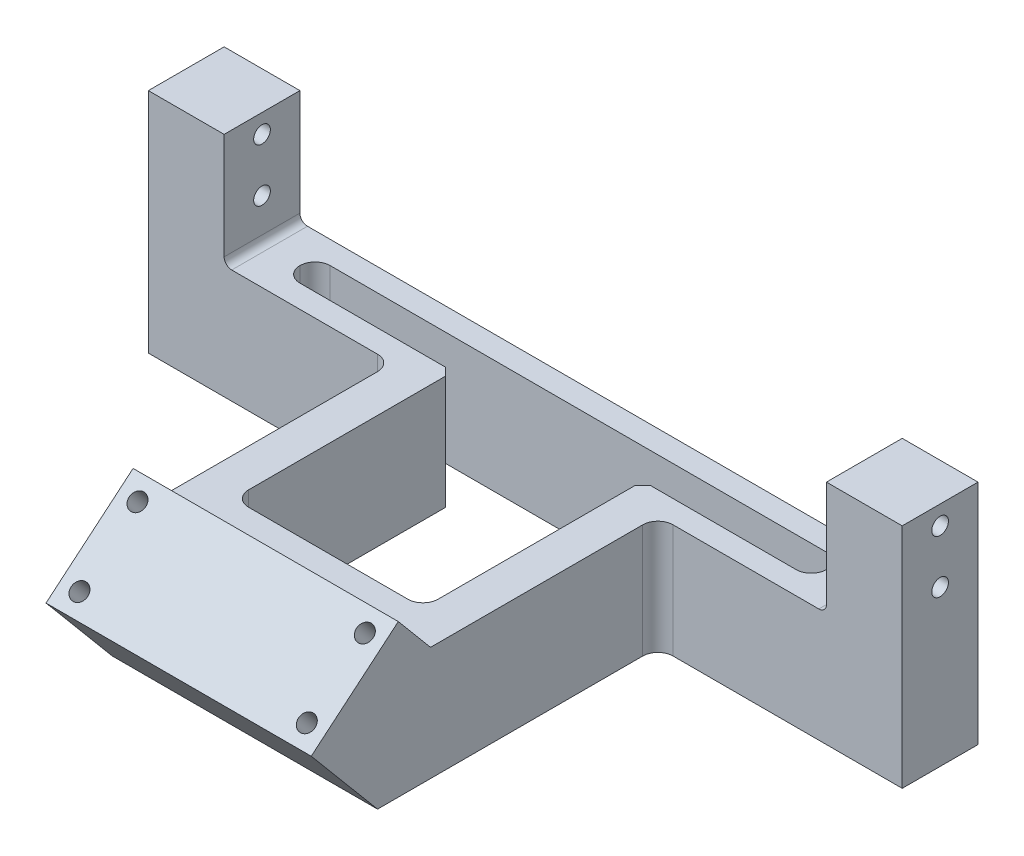
SolidWorks part; units mm, degrees
material "PLA"
ref_plane "Front Plane" through (0, 0, 0) normal (0, 0, 1) x (1, 0, 0)
ref_plane "Top Plane" through (0, 0, 0) normal (0, 1, 0) x (1, 0, 0)
ref_plane "Right Plane" through (0, 0, 0) normal (1, 0, 0) x (0, 0, -1)
sketch "Sketch1" plane through (0, 0, 0) normal (0, 0, 1) x (1, 0, 0)
  line L0 (63.1698, 0) -> (-63.1698, 0)
  line L1 (-63.1698, 0) -> (-63.1698, 38.1)
  line L2 (-63.1698, 38.1) -> (-50.4698, 38.1)
  line L3 (-50.4698, 38.1) -> (-50.4698, 19.05)
  line L4 (-50.4698, 19.05) -> (50.4698, 19.05)
  line L5 (0, 19.05) -> (0, 0) construction
  line L6 (50.4698, 38.1) -> (50.4698, 19.05)
  line L7 (63.1698, 38.1) -> (50.4698, 38.1)
  line L8 (63.1698, 0) -> (63.1698, 38.1)
  dimension "D1" = 19.05
  dimension "D2" = 12.7
  dimension "D3" = 126.3396
  dimension "D4" = 38.1
extrude "Boss-Extrude1" add sketch "Sketch1" along normal blind 12.7
sketch "Sketch2" plane through (-63.1698, 0, 0) normal (-1, 0, 0) x (0, 0, 1)
  line L0 (6.35, 38.1) -> (6.35, 0) construction
  line L1 (12.7, 38.1) -> (0, 38.1) construction
  line L2 (12.7, 0) -> (0, 0) construction
  circle A0 centre (6.35, 34.925) radius 1.397
  circle A1 centre (6.35, 26.035) radius 1.397
  dimension "D1" = 2.794
  dimension "D2" = 2.794
  dimension "D3" = 8.89
  dimension "D4" = 3.175
extrude "Cut-Extrude1" cut sketch "Sketch2" against normal through all
fillet "Fillet1" radius 1.27 2 edges at (50.4698, 19.05, 6.35) (-50.4698, 19.05, 6.35)
sketch "Sketch3" plane through (0, 0, 0) normal (1, 0, 0) x (0, 0, -1)
  line L0 (0, 19.05) -> (-12.7, 19.05) construction
  line L1 (0, 19.05) -> (-12.7, 19.05) construction
  line L2 (-12.7, 19.05) -> (-12.7, 0)
  line L3 (-12.7, 0) -> (-59.6832, 0)
  line L4 (-12.7, 19.05) -> (-50.8, 19.05)
  line L5 (-50.8, 19.05) -> (-56.2034, 25.4896)
  line L6 (-56.2034, 25.4896) -> (-70.7966, 13.2444)
  line L7 (-70.7966, 13.2444) -> (-59.6832, 0)
  point P7 (-63.5, 19.367)
  dimension "D1" = 50
  dimension "D2" = 50.8
  dimension "D3" = 38.1
extrude "Boss-Extrude2" add sketch "Sketch3" along normal mid plane 44.45
sketch "Sketch6" plane through (0, 19.05, 0) normal (0, 1, 0) x (1, 0, 0)
  line L0 (0, 0) -> (0, -50.8) construction
  line L1 (49.1998, 0) -> (-49.1998, 0) construction
  line L2 (22.225, -50.8) -> (-22.225, -50.8) construction
  line L3 (44.1198, -3.81) -> (-44.1198, -3.81)
  line L4 (-44.1198, -3.81) -> (-44.1198, -8.89)
  line L5 (-44.1198, -8.89) -> (-15.875, -8.89)
  line L6 (-15.875, -8.89) -> (-15.875, -45.72)
  line L7 (-15.875, -45.72) -> (15.875, -45.72)
  line L8 (-22.225, -12.7) -> (-49.1998, -12.7) construction
  line L9 (-22.225, -12.7) -> (-22.225, -50.8) construction
  line L10 (-49.1998, 0) -> (-49.1998, -12.7) construction
  line L11 (15.875, -8.89) -> (15.875, -45.72)
  line L12 (44.1198, -8.89) -> (15.875, -8.89)
  line L13 (44.1198, -3.81) -> (44.1198, -8.89)
  point P18 (-49.1998, -6.35)
  point P20 (0, -45.72)
  point P23 (0, -3.81)
  dimension "D1" = 3.81
  dimension "D2" = 3.81
  dimension "D3" = 6.35
  dimension "D4" = 5.08
  dimension "D5" = 5.08
extrude "Cut-Extrude3" cut sketch "Sketch6" against normal through all
fillet "Fillet3" radius 2.54 8 edges at (44.1198, 9.525, 8.89) (44.1198, 9.525, 3.81) (15.875, 9.525, 45.72) (-15.875, 9.525, 45.72) (-44.1198, 9.525, 8.89) (-44.1198, 9.525, 3.81) (22.225, 9.525, 12.7) (-22.225, 9.525, 12.7)
chamfer "Chamfer1" distance 1.27 angle 45 2 edges at (15.875, 9.525, 8.89) (-15.875, 9.525, 8.89)
sketch "Sketch7" plane through (0, 42.6327, 35.7731) normal (0, 0.766, 0.6428) x (1, 0, 0)
  line L0 (0, -26.67) -> (0, -45.72) construction
  line L1 (22.225, -26.67) -> (-22.225, -26.67) construction
  line L2 (22.225, -45.72) -> (-22.225, -45.72) construction
  line L3 (-22.225, -36.195) -> (22.225, -36.195) construction
  line L4 (-22.225, -26.67) -> (-22.225, -45.72) construction
  line L5 (22.225, -26.67) -> (22.225, -45.72) construction
  circle A0 centre (-19.05, -29.845) radius 1.397
  circle A1 centre (-19.05, -42.545) radius 1.397
  circle A2 centre (19.05, -42.545) radius 1.397
  circle A3 centre (19.05, -29.845) radius 1.397
  dimension "D1" = 2.794
  dimension "D2" = 12.7
  dimension "D3" = 38.1
extrude "Cut-Extrude4" cut sketch "Sketch7" against normal mid plane 12.7
equation "\"D2@Sketch6\"=\"D1@Sketch6\""
equation "\"D5@Sketch6\"=\"D4@Sketch6\""
